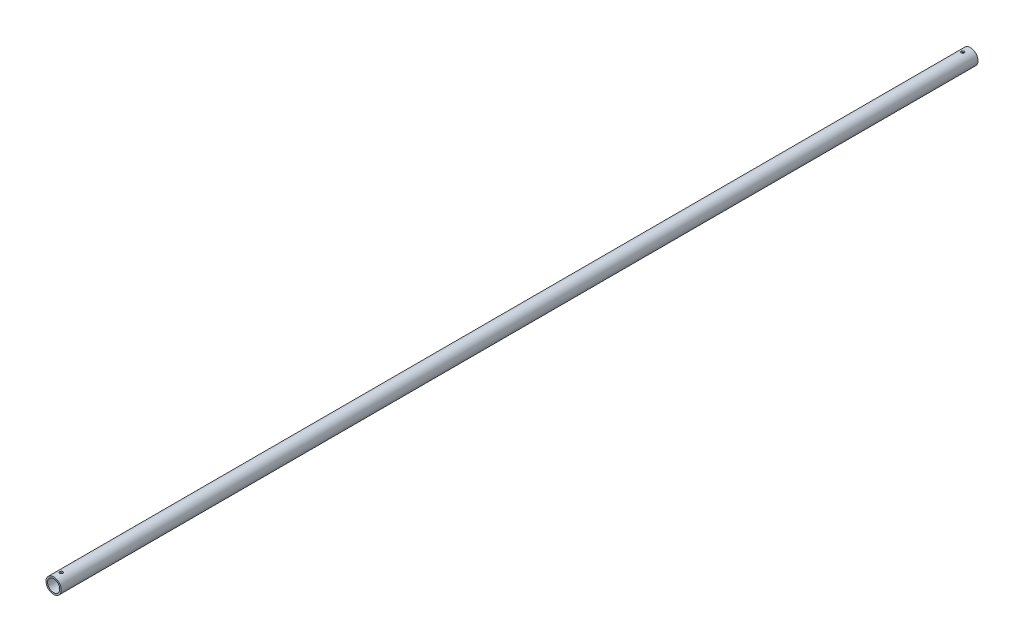
SolidWorks part; units mm, degrees
material "Thornel Mat VMA"
ref_plane "前视基准面" through (0, 0, 0) normal (0, 0, 1) x (1, 0, 0)
ref_plane "上视基准面" through (0, 0, 0) normal (0, 1, 0) x (1, 0, 0)
ref_plane "右视基准面" through (0, 0, 0) normal (1, 0, 0) x (0, 0, -1)
sketch "草图1" plane through (0, 0, 0) normal (0, 0, 1) x (1, 0, 0)
  circle A0 centre (0, 0) radius 4
  circle A1 centre (0, 0) radius 5
  dimension "D1" = 8
  dimension "D2" = 10
extrude "凸台-拉伸1" add sketch "草图1" along normal blind 300 and the other way blind 300
sketch "草图3" plane through (0, 0, 0) normal (0, 1, 0) x (1, 0, 0)
  line L0 (5, 300) -> (-5, 300) construction
  line L1 (-1000, 0) -> (49000, 0) construction
  circle A0 centre (0, 295) radius 1
  circle A1 centre (0, -295) radius 1
  dimension "D1" = 2
  dimension "D2" = 5
extrude "切除-拉伸2" cut sketch "草图3" against normal through all and the other way through all
sketch "草图5" plane through (0, 0, 0) normal (0, 1, 0) x (1, 0, 0)
  circle A0 centre (0, 0) radius 20.9079
